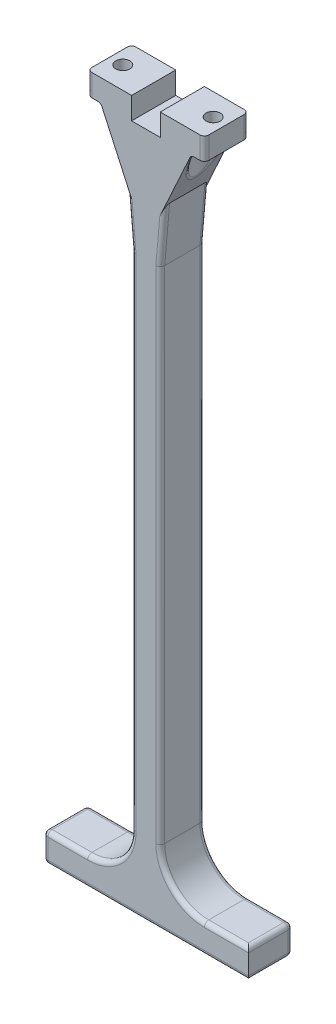
SolidWorks part; units mm, degrees
other "Markup1"
sketch "Sketch10" plane through (10, 5, 30) normal (0.8578, 0.2314, 0.4589) x (0.503, -0.1946, -0.8421)
material "PLA Black"
ref_plane "Front Plane" through (0, 0, 0) normal (0, 0, 1) x (1, 0, 0)
ref_plane "Top Plane" through (0, 0, 0) normal (0, 1, 0) x (1, 0, 0)
ref_plane "Right Plane" through (0, 0, 0) normal (1, 0, 0) x (0, 0, -1)
sketch "Sketch1" plane through (0, 0, 0) normal (0, 0, 1) x (1, 0, 0)
  line L0 (0, 0) -> (0, 5)
  line L2 (10, 5) -> (10, 0)
  line L8 (-16.5, 0) -> (-16.5, 5)
  line L10 (-6.5, 5) -> (-6.5, 0)
  line L11 (-6.5, 0) -> (0, 0)
  line L39 (-6.5, -155.6783) -> (0, -155.6783)
  line L40 (-3.25, -155.6783) -> (-3.25, -166.0309) construction
  line L48 (10, 0) -> (2.25, 0)
  line L49 (-16.5, 0) -> (-8.75, 0)
  line L50 (-8.75, 0) -> (-6.5, -25.6783)
  line L51 (-16.5, 5) -> (-6.5, 5)
  line L52 (0, -25.6783) -> (2.25, 0)
  line L53 (0, -25.6783) -> (0, -155.6783)
  line L54 (-6.5, -155.6783) -> (-6.5, -25.6783)
  line L56 (0, 5) -> (10, 5)
  point P6 (-3.25, 0)
  dimension "D13" = 130
  dimension "D10" = 2.25
  dimension "D1" = 6.5
  dimension "D8" = 155.6783
  dimension "D9" = 6.5
  dimension "D11" = 6.5
  dimension "D15" = 130
extrude "Boss-Extrude1" add sketch "Sketch1" along normal blind 10
sketch "Sketch5" plane through (0, 0, 10) normal (0, 0, 1) x (1, 0, 0)
  line L0 (0, -155.6783) -> (0, -25.6783) construction
  line L1 (-6.5, -155.6783) -> (0, -155.6783)
  line L2 (-6.5, -155.6783) -> (-6.5, -149.1783)
  line L3 (-6.5, -149.1783) -> (0, -149.1783)
  line L4 (0, -155.6783) -> (0, -149.1783)
  dimension "D1" = 6.5
extrude "Boss-Extrude2" add sketch "Sketch5" along normal blind 20 and the other way blind 26.5
fillet "Fillet1" radius 5 2 edges at (-3.25, -149.1783, 0) (-3.25, -149.1783, 10)
sketch "Sketch6" plane through (0, 5, 0) normal (0, 1, 0) x (1, 0, 0)
  line L0 (10, -10) -> (10, 0) construction
  line L1 (-16.5, -10) -> (-16.5, 0) construction
  line L2 (-16.5, -5) -> (12.5953, -5) construction
  circle A0 centre (7, -5) radius 1.6
  circle A1 centre (-13.5, -5) radius 1.6
  dimension "D1" = 3.2
  dimension "D2" = 3.2
  dimension "D3" = 3
  dimension "D4" = 3
extrude "Cut-Extrude3" cut sketch "Sketch6" against normal blind 5
sketch "Sketch9" plane through (0, 0, 0) normal (0, 0, -1) x (-1, 0, 0)
  line L0 (13.5, 0) -> (7.625, -12.8392)
  line L1 (11.9, 0) -> (15.1, 0) construction
  line L2 (8.75, 0) -> (6.5, -25.6783) construction
  line L3 (3.25, 0) -> (3.25, -9.9949)
  line L4 (0, 0) -> (6.5, 0) construction
  line L5 (7.625, -12.8392) -> (8.75, 0)
  line L6 (8.75, 0) -> (13.5, 0)
  line L7 (-1.125, -12.8392) -> (-2.25, 0)
  line L8 (-7, 0) -> (-1.125, -12.8392)
  line L9 (-2.25, 0) -> (-7, 0)
extrude "Boss-Extrude3" add sketch "Sketch9" against normal up to surface (10 mm away) contours L6 L0 L5 | L7 L9 L8 up to face at (-3.25, -22.8367, 10)
sketch "Sketch8" plane through (0, 0, 0) normal (0, -1, 0) x (1, 0, 0)
  line L14 (-13.5, 9) -> (-13.5, 1)
  line L15 (-3.25, 30) -> (-3.25, -22.9012) construction
  line L16 (-6.5, 30) -> (0, 30) construction
  line L17 (7, 9) -> (7, 1)
  arc A0 (-13.5, 1) -> (-13.5, 9) centre (-13.5, 5) ccw
  arc A1 (7, 1) -> (7, 9) centre (7, 5) cw
  dimension "D1" = 8
extrude "Cut-Extrude4" cut sketch "Sketch8" along normal blind 10
fillet "Fillet2" radius 1 8 edges at (7, 0, 0.5) (7, 0, 9.5) (-13.5, 0, 0.5) (-13.5, 0, 9.5) (3, -8.7416, 5) (3, 0, 5) (-9.5, 0, 5) (-9.5, -8.7416, 5)
sketch "Sketch11" plane through (0, 5, 0) normal (0, 1, 0) x (1, 0, 0)
  line L1 (-21.2413, -31.4753) -> (15.0393, -31.4753)
  line L2 (-21.2413, -31.4753) -> (-21.2413, 21.4753)
  line L3 (-21.2413, 21.4753) -> (15.0393, 21.4753)
  line L4 (15.0393, -31.4753) -> (15.0393, 21.4753)
  line L7 (-16.5, -10) -> (10, -10)
  line L8 (-16.5, -10) -> (-16.5, 0)
  line L9 (-16.5, 0) -> (10, 0)
  line L10 (10, -10) -> (10, 0)
  point P0 (-3.101, -5)
  dimension "D1" = 52.9507
  dimension "D2" = 36.2806
  dimension "D3" = 21.4753
  dimension "D4" = 5.0393
extrude "Cut-Extrude9" cut sketch "Sketch11" along normal blind 20 from surface starting at face at (-3.25, -155.6783, 6.75)
sketch "Sketch12" plane through (0, 0, 10) normal (0, 0, 1) x (1, 0, 0)
  line L0 (0, -149.1783) -> (20, -149.1783)
  line L1 (0, -155.6783) -> (0, -25.6783) construction
  line L2 (20, -149.1783) -> (20, -155.6783)
  line L3 (-26.5, -155.6783) -> (-6.5, -155.6783)
  line L4 (-26.5, -155.6783) -> (-26.5, -149.1783)
  line L5 (-26.5, -149.1783) -> (-6.5, -149.1783)
  line L6 (-6.5, -25.6783) -> (-6.5, -155.6783) construction
  line L8 (0, -155.6783) -> (20, -155.6783)
  line L9 (-6.5, -155.6783) -> (-6.5, -149.1783)
  line L10 (0, -155.6783) -> (0, -149.1783)
  dimension "D1" = 6.5
  dimension "D2" = 20
  dimension "D3" = 20
extrude "Boss-Extrude4" add sketch "Sketch12" against normal up to surface (10 mm away) up to face at (-3.25, -20.5163, 0)
fillet "Fillet3" radius 10 2 edges at (-6.5, -149.1783, 5) (0, -149.1783, 5)
fillet "Fillet5" radius 1 29 edges at (0, -82.4283, 10) (2.9289, -146.2494, 10) (0, -82.4283, 0) (15, -149.1783, 0) (-6.5, -82.4283, 0) (-9.4289, -146.2494, 0) (-6.5, -82.4283, 10) (-9.4289, -146.2494, 10) (10, 2.5, 10) (10, 2.5, 0) (-16.5, 2.5, 10) (-16.5, 2.5, 0) (20, -152.4283, 0) (-26.5, -149.1783, 5) (-26.5, -152.4283, 10) (-26.5, -152.4283, 0) (-3.25, -155.6783, 0) (-26.5, -155.6783, 5) (-3.25, -155.6783, 10) (20, -155.6783, 5) (20, -149.1783, 5) (15, -149.1783, 10) (2.9289, -146.2494, 0) (-21.5, -149.1783, 0) (-21.5, -149.1783, 10) (-7.0625, -19.2587, 10) (-7.0625, -19.2587, 0) (0.5625, -19.2587, 10) (0.5625, -19.2587, 0)
